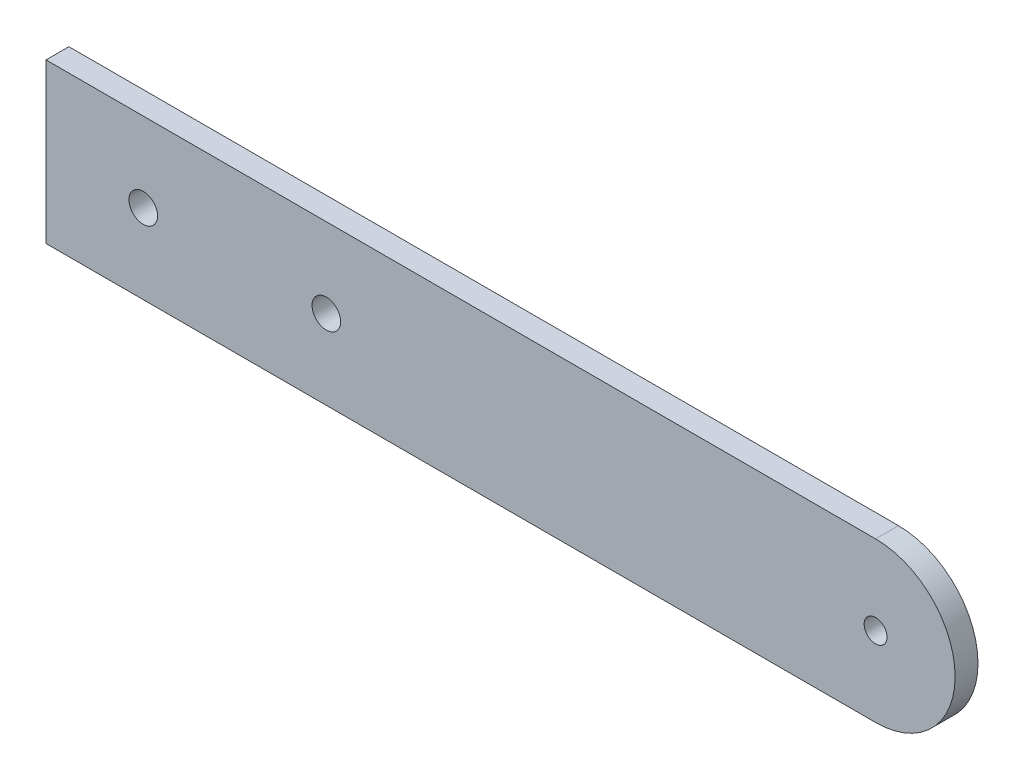
SolidWorks part; units mm, degrees
ref_plane "前视基准面" through (0, 0, 0) normal (0, 0, 1) x (1, 0, 0)
ref_plane "上视基准面" through (0, 0, 0) normal (0, 1, 0) x (1, 0, 0)
ref_plane "右视基准面" through (0, 0, 0) normal (1, 0, 0) x (0, 0, -1)
sketch "草图1" plane through (0, 0, 0) normal (0, 0, 1) x (1, 0, 0)
  line L0 (-75.5387, 0) -> (52.4613, 0) construction
  line L1 (-75.5387, 13.9) -> (52.4613, 13.9)
  line L2 (-75.5387, -13.9) -> (52.4613, -13.9)
  line L3 (-75.5387, 13.9) -> (-92.5387, 13.9)
  line L4 (-92.5387, 13.9) -> (-92.5387, -13.9)
  line L5 (-92.5387, -13.9) -> (-75.5387, -13.9)
  arc A1 (52.4613, -13.9) -> (52.4613, 13.9) centre (52.4613, 0) ccw
  circle A2 centre (-75.5387, 0) radius 2.5
  circle A3 centre (52.4613, 0) radius 2
  circle A4 centre (-43.5387, 0) radius 2.5
  point P3 (2.4613, 0)
  dimension "D1" = 128
  dimension "D2" = 4
  dimension "D3" = 5
  dimension "D4" = 13.9
  dimension "D5" = 5
  dimension "D6" = 32
  dimension "D7" = 17
extrude "凸台-拉伸1" add sketch "草图1" along normal blind 4
